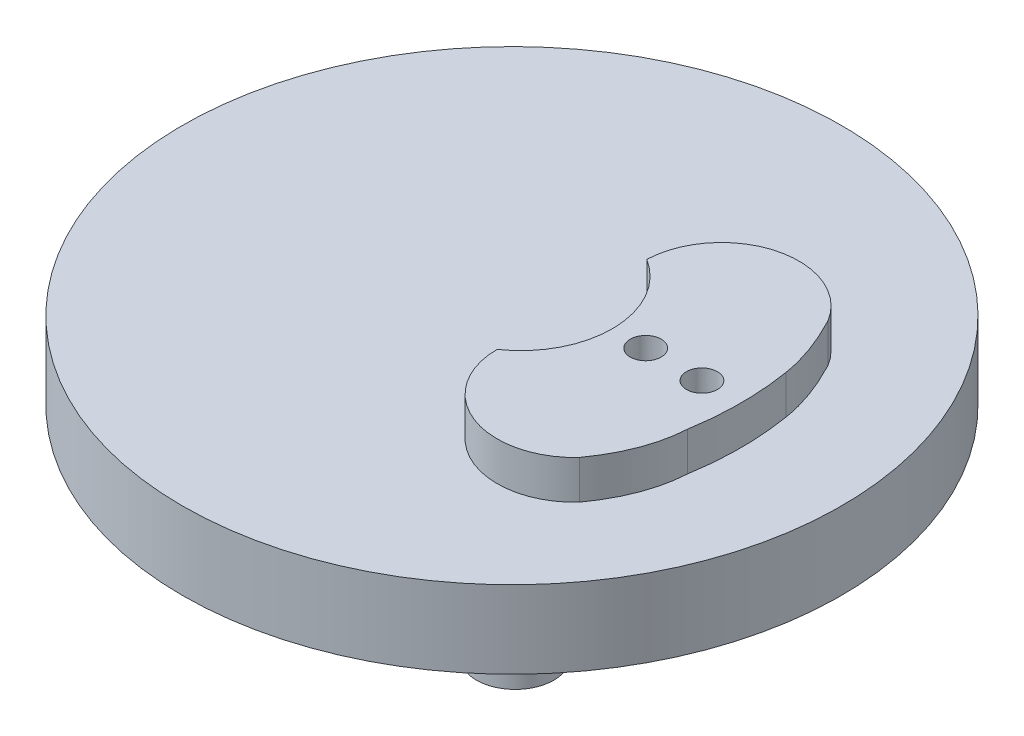
SolidWorks part; units mm, degrees
ref_plane "Front Plane" through (0, 0, 0) normal (0, 0, 1) x (1, 0, 0)
ref_plane "Top Plane" through (0, 0, 0) normal (0, 1, 0) x (1, 0, 0)
ref_plane "Right Plane" through (0, 0, 0) normal (1, 0, 0) x (0, 0, -1)
sketch "Sketch1" plane through (0, 0, 0) normal (0, 1, 0) x (1, 0, 0)
  circle A0 centre (0, 0) radius 42.5
  dimension "D1" = 85
extrude "Boss-Extrude1" add sketch "Sketch1" along normal blind 10
sketch "Sketch2" plane through (0, 0, 0) normal (0, -1, 0) x (1, 0, 0)
  circle A5 centre (-21.0033, 21.421) radius 5
  circle A6 centre (21.421, 21.0033) radius 5
  circle A7 centre (21.0033, -21.421) radius 5
  circle A8 centre (-21.421, -21.0033) radius 5
  point P12 (0, 0)
  point P16 (0, 0)
  dimension "D1" = 4
  dimension "D4" = 10
extrude "Boss-Extrude2" add sketch "Sketch2" along normal blind 7
sketch "Sketch3" plane through (0, 10, 0) normal (0, 1, 0) x (1, 0, 0)
  circle A0 centre (17.25, 0) radius 2
  circle A1 centre (24.5, 0) radius 2
  arc A5 (7.8151, -9.7199) -> (25.9581, -15.5245) centre (17.8151, -9.7199) ccw
  circle A6 centre (0, 0) radius 42.5
  circle A7 centre (0, 0) radius 42.5
  arc A10 (26.6881, 13.3259) -> (7.4106, 9.9848) centre (17.4036, 9.6111) ccw
  arc A11 (7.8151, -9.7199) -> (7.4106, 9.9848) centre (1.1616, 0) ccw
  spline S0 degree 3 poles (25.9558, 14.7939) (27.3295, 12.1453) (28.5409, 9.3136) (29, 6.35) knots 0 0 0 0 0.277553 0.277553 0.277553 0.277553
  spline S1 degree 2 poles (29, 6.35) (30.0423, 0) (29, -6.35) knots 0 0 0 1 1 1
  spline S3 degree 2 poles (29, -6.35) (28.6991, -11.6005) (25.178, -16.4866) knots 0.672683 0.672683 0.672683 1 1 1
  point P0 (0, 0)
  point P14 (0, -0.1316)
  dimension "D9" = 4
  dimension "D10" = 4
  dimension "D16" = 20
  dimension "D3" = 17.25
  dimension "D5" = 7.25
  dimension "D15" = 0
extrude "Boss-Extrude3" add sketch "Sketch3" along normal blind 5 contours S3 S1 S0 A10 A11 A5 A1 A0 region at (13.3893, 10, -0.251)
extrude "Cut-Extrude1" cut sketch "Sketch3<4>" against normal through all both and the other way through all contours A1 | A0 region at (17.25, 10, 0) region at (24.5, 10, 0)
sketch "Sketch3<4>" plane through (0, 10, 0) normal (0, 1, 0) x (1, 0, 0) same geometry as "Sketch3"
